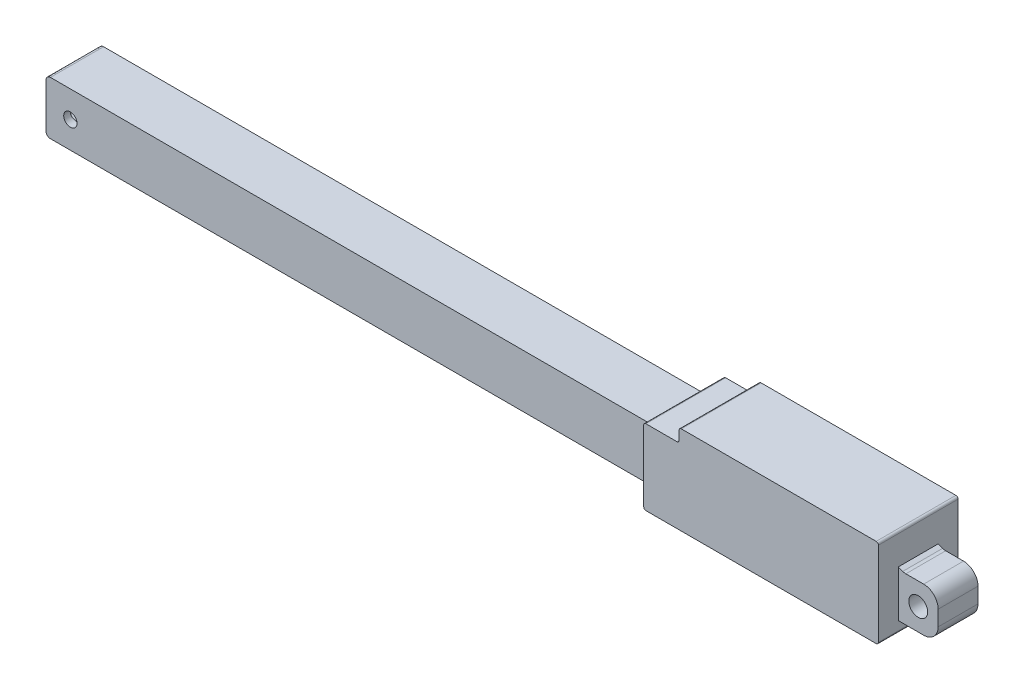
SolidWorks part; units mm, degrees
ref_plane "Front Plane" through (0, 0, 0) normal (0, 0, 1) x (1, 0, 0)
ref_plane "Top Plane" through (0, 0, 0) normal (0, 1, 0) x (1, 0, 0)
ref_plane "Right Plane" through (0, 0, 0) normal (1, 0, 0) x (0, 0, -1)
sketch "Sketch2" plane through (0, 0, 0) normal (0, 0, 1) x (1, 0, 0)
  line L0 (138, 12) -> (138, 14)
  line L1 (1, 0) -> (138, 0)
  line L2 (0, 1) -> (0, 11)
  line L3 (1, 12) -> (138, 12)
  line L4 (138, 0) -> (138, 12)
  line L5 (138, 0) -> (138, -2)
  line L6 (138.5, -2.5) -> (190.5, -2.5)
  line L7 (191, -2) -> (191, 17)
  line L8 (190.5, 17.5) -> (146.5, 17.5)
  line L9 (146, 17) -> (146, 15)
  line L10 (145.5, 14.5) -> (138.5, 14.5)
  line L11 (191, 0) -> (196.7317, 0)
  line L12 (200, 3.2683) -> (200, 6.7317)
  line L13 (196.7317, 10) -> (192.6999, 10)
  line L14 (192, 10.1265) -> (191, 10.5)
  line L15 (195.5, 0) -> (195.5, 10) construction
  line L16 (2, 12) -> (2, 0)
  line L18 (2, 6) -> (4, 6) construction
  line L19 (0, 6) -> (2, 6) construction
  arc A0 (0, 11) -> (1, 12) centre (1, 11) cw
  arc A1 (1, 0) -> (0, 1) centre (1, 1) cw
  arc A2 (146.5, 17.5) -> (146, 17) centre (146.5, 17) ccw
  arc A3 (191, 17) -> (190.5, 17.5) centre (190.5, 17) ccw
  arc A4 (190.5, -2.5) -> (191, -2) centre (190.5, -2) ccw
  arc A5 (138, -2) -> (138.5, -2.5) centre (138.5, -2) ccw
  arc A6 (138, 14) -> (138.5, 14.5) centre (138.5, 14) cw
  arc A7 (146, 15) -> (145.5, 14.5) centre (145.5, 15) cw
  arc A8 (196.7317, 0) -> (200, 3.2683) centre (196.7317, 3.2683) ccw
  arc A9 (200, 6.7317) -> (196.7317, 10) centre (196.7317, 6.7317) ccw
  circle A10 centre (195.5, 5) radius 2.125
  arc A11 (192.6999, 10) -> (192, 10.1265) centre (192.6999, 12) cw
  circle A12 centre (5.5, 6) radius 1.5
  point P7 (0, 12)
  point P10 (0, 0)
  point P23 (191, -2.5)
  point P26 (138, -2.5)
  point P29 (138, 14.5)
  point P32 (146, 14.5)
  point P44 (195.5, 5)
  point P54 (4, 6)
  dimension "D3" = 1
  dimension "D8" = 0.5
  dimension "D12" = 4.25
  dimension "D13" = 2
  dimension "D14" = 3
  dimension "D1" = 138
  dimension "D2" = 12
  dimension "D4" = 53
  dimension "D5" = 17
  dimension "D6" = 20
  dimension "D7" = 8
  dimension "D9" = 9
  dimension "D10" = 10
  dimension "D11" = 4.5
  dimension "D15" = 2
  dimension "D16" = 1
  dimension "D17" = 0.5
extrude "Boss-Extrude1" add sketch "Sketch2" along normal mid plane 18 contours L9 A7 L10 A6 L0 L4 L5 A5 L6 A4 L7 A3 L8 A2 region at (165.0213, 7.3031, 0)
extrude "Boss-Extrude2" add sketch "Sketch2<3>" along normal mid plane 12 contours L3 L16 L1 L4 A12 region at (70.2806, 6, 0)
sketch "Sketch2<3>" plane through (0, 0, 0) normal (0, 0, 1) x (1, 0, 0) same geometry as "Sketch2"
extrude "Boss-Extrude3" add sketch "Sketch2<4>" along normal mid plane 12 contours A1 L1 L16 L3 A0 L2 region at (1.0141, 6, 0)
sketch "Sketch2<4>" plane through (0, 0, 0) normal (0, 0, 1) x (1, 0, 0) same geometry as "Sketch2"
extrude "Boss-Extrude4" add sketch "Sketch2<5>" along normal mid plane 9 contours L13 A11 L14 L7 L11 A8 L12 A9 A10 region at (191.1383, 5.25, 0)
sketch "Sketch2<5>" plane through (0, 0, 0) normal (0, 0, 1) x (1, 0, 0) same geometry as "Sketch2"
sketch "Sketch3" plane through (0, 0, 0) normal (-1, 0, 0) x (0, 0, 1)
  line L0 (-6, 1) -> (-4.5, 1)
  line L1 (6, 1) -> (-6, 1) construction
  line L2 (-4.5, 1) -> (-4.5, 1.5)
  line L4 (-4.5, 1.5) -> (4.5, 1.5)
  line L5 (-4.5, 1.5) -> (-4.5, 10.5)
  line L6 (-4.5, 10.5) -> (4.5, 10.5)
  line L7 (4.5, 1.5) -> (4.5, 10.5)
  dimension "D1" = 1.5
  dimension "D2" = 9
  dimension "D3" = 9
  dimension "D4" = 0.5
sketch "Sketch7" plane through (0, 0, 0) normal (-1, 0, 0) x (0, 0, 1)
  line L0 (0, 1) -> (6, 6) construction
  line L1 (6, 1) -> (-6, 1) construction
  line L2 (6, 1) -> (6, 11) construction
  line L3 (6, 6) -> (0, 6) construction
  circle A0 centre (0, 6) radius 4.5
  dimension "D1" = 9
extrude "Cut-Extrude4" cut sketch "Sketch7" against normal blind 138
